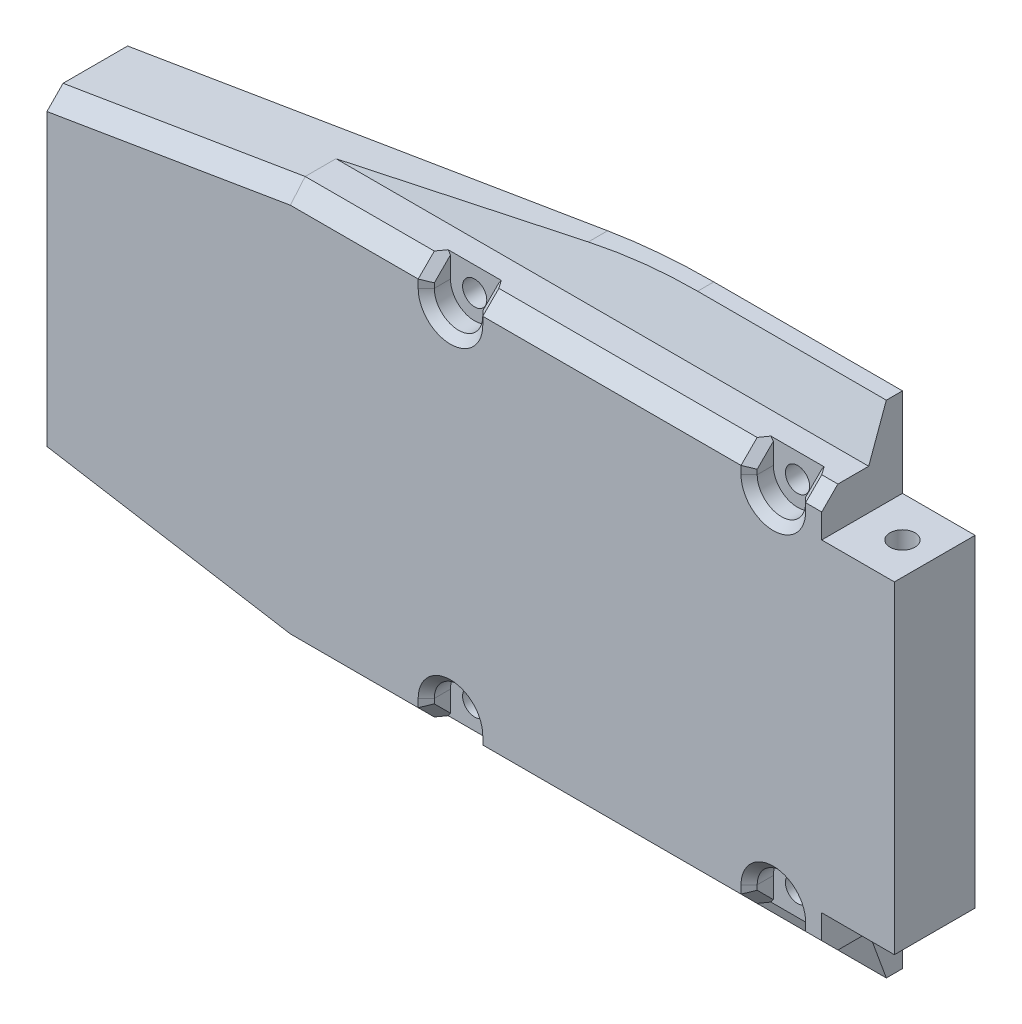
SolidWorks part; units mm, degrees
material "ABS"
ref_plane "Ebene vorne" through (0, 0, 0) normal (0, 0, 1) x (1, 0, 0)
ref_plane "Ebene oben" through (0, 0, 0) normal (0, 1, 0) x (1, 0, 0)
ref_plane "Ebene rechts" through (0, 0, 0) normal (1, 0, 0) x (0, 0, -1)
sketch "Skizze2" plane through (0, 0, 0) normal (0, 0, 1) x (1, 0, 0)
  line L0 (-151.7782, 0) -> (154.8922, 0) construction
  line L1 (0, 106.9611) -> (0, -93.0562) construction
  line L2 (0, 25) -> (-75, 25)
  line L3 (-75, 25) -> (-105, 20)
  line L4 (-105, 20) -> (-105, 11)
  line L5 (-105, 11) -> (-98, 11)
  line L6 (-95, 8) -> (-95, -8)
  line L7 (0, 25) -> (0, -25)
  line L8 (-105, -11) -> (-98, -11)
  line L9 (-105, -20) -> (-105, -11)
  line L10 (-75, -25) -> (-105, -20)
  line L11 (0, -25) -> (-75, -25)
  arc A0 (-98, -11) -> (-95, -8) centre (-98, -8) ccw
  arc A1 (-95, 8) -> (-98, 11) centre (-98, 8) ccw
  point P13 (0, 0)
  point P14 (-95, 0)
  point P19 (-95, -11)
  point P22 (-95, 11)
  dimension "D7" = 3
  dimension "D1" = 105
  dimension "D2" = 50
  dimension "D3" = 40
  dimension "D4" = 30
  dimension "D5" = 22
  dimension "D6" = 10
extrude "Aufsatz-Linear austragen1" add sketch "Skizze2" along normal blind 5 and the other way blind 5
hole_wizard "Ø3.1 (3.1) Durchmesser Bohrung1" positions "Skizze4" profile "Skizze3" hole size "Ø3.1" standard "ANSI Metrisch"
sketch "Skizze4" plane through (-105, 0, 0) normal (-1, 0, 0) x (0, 0, 1)
  line L0 (0, 37.8153) -> (0, -33.0973) construction
  line L3 (-22.117, 0) -> (22.0161, 0) construction
  point P0 (0, 15)
  point P14 (0, -15)
  dimension "D1" = 30
sketch "Skizze3" plane through (-105, 15, 0) normal (0, 1, 0) x (0, 0, 1)
  line L0 (0, 0) -> (0, 8.9313)
  line L1 (0, 8.9313) -> (1.55, 8)
  line L2 (1.55, 8) -> (1.55, 0)
  line L5 (1.55, 0) -> (0, 0)
  line L10 (0, 8.9313) -> (-1.55, 8) construction
  line L11 (0, -6.35) -> (0, 107.95) construction
  dimension "Bohrerdurchmesser" = 3.1
  dimension "Bohrungstiefe" = 8
  dimension "Spitzenwinkel" = 118
sketch "Skizze5" plane through (0, 0, 0) normal (0, 0, 1) x (1, 0, 0)
  line L0 (-134.3407, 0) -> (33.9152, 0) construction
  line L1 (0, 49.9151) -> (0, -37.4044) construction
  circle A0 centre (-55, 22) radius 1.5
  circle A1 centre (-15, 22) radius 1.5
  circle A2 centre (-15, -22) radius 1.5
  circle A3 centre (-55, -22) radius 1.5
  dimension "D1" = 3
  dimension "D2" = 40
  dimension "D3" = 15
  dimension "D4" = 22
extrude "Schnitt-Linear austragen1" cut sketch "Skizze5" against normal through all and the other way through all
sketch "Skizze6" plane through (0, 0, 5) normal (0, 0, 1) x (1, 0, 0)
  line L0 (-55, 22) -> (-55, 29.2626) construction
  line L1 (-58, 22) -> (-58, 29.2626)
  line L2 (-52, 22) -> (-52, 29.2626)
  line L3 (-15, 22) -> (-15, 29.2626) construction
  line L4 (-18, 22) -> (-18, 29.2626)
  line L5 (-12, 22) -> (-12, 29.2626)
  line L6 (-55, -22) -> (-55, -29.7807) construction
  line L7 (-52, -22) -> (-52, -29.7807)
  line L8 (-58, -22) -> (-58, -29.7807)
  line L9 (-15, -22) -> (-15, -30.8486) construction
  line L10 (-12, -22) -> (-12, -30.8486)
  line L11 (-18, -22) -> (-18, -30.8486)
  arc A4 (-58, 22) -> (-52, 22) centre (-55, 22) ccw
  arc A5 (-52, 29.2626) -> (-58, 29.2626) centre (-55, 29.2626) ccw
  arc A6 (-18, 22) -> (-12, 22) centre (-15, 22) ccw
  arc A7 (-12, 29.2626) -> (-18, 29.2626) centre (-15, 29.2626) ccw
  arc A8 (-52, -22) -> (-58, -22) centre (-55, -22) ccw
  arc A9 (-58, -29.7807) -> (-52, -29.7807) centre (-55, -29.7807) ccw
  arc A10 (-12, -22) -> (-18, -22) centre (-15, -22) ccw
  arc A11 (-18, -30.8486) -> (-12, -30.8486) centre (-15, -30.8486) ccw
  point P6 (-15, 25.6313)
  point P12 (-55, 25.6313)
  point P19 (-55, -25.8903)
  point P28 (-15, -26.4243)
  dimension "D1" = 3
extrude "Schnitt-Linear austragen2" cut sketch "Skizze6" against normal blind 3
sketch "Skizze7" plane through (0, 0, 5) normal (0, 0, 1) x (1, 0, 0)
  line L0 (-130.6386, 0) -> (13.2343, 0) construction
  line L1 (0, 46.5959) -> (0, -35.1065) construction
  line L2 (0, 25) -> (-9, 25)
  line L3 (0, 25) -> (-12, 25) construction
  line L4 (-9, 25) -> (-9, 20)
  line L5 (-9, 20) -> (0, 20)
  line L6 (0, 20) -> (0, 25)
  line L7 (0, -20) -> (0, -25)
  line L8 (-9, -20) -> (0, -20)
  line L9 (-9, -25) -> (-9, -20)
  line L10 (0, -25) -> (-9, -25)
  dimension "D1" = 5
  dimension "D2" = 9
extrude "Schnitt-Linear austragen3" cut sketch "Skizze7" against normal through all and the other way through all
sketch "Skizze8" plane through (0, 0, 0) normal (0, 0, 1) x (1, 0, 0)
  line L0 (-143.7875, 0) -> (29.5748, 0) construction
  line L1 (0, 40.8512) -> (0, -33.9576) construction
  line L17 (-55, 30.597) -> (-55, -26.6464) construction
  line L18 (-51, -22) -> (-19, -22)
  line L19 (-56, 18.127) -> (-56, -18.127)
  line L20 (-54, 18.127) -> (-54, -18.127)
  line L21 (-59, -22) -> (-74.7517, -22)
  line L22 (-74.7517, -22) -> (-93, -18.9586)
  line L23 (-93, -18.9586) -> (-93, 18.9586)
  line L24 (-75, -25) -> (-58, -25) construction
  line L25 (-105, -20) -> (-75, -25) construction
  line L26 (-95, 8) -> (-95, -8) construction
  line L27 (-74.7517, 22) -> (-93, 18.9586)
  line L28 (-59, 22) -> (-74.7517, 22)
  line L29 (-51, 22) -> (-19, 22)
  line L30 (-15, -18) -> (-7, -18)
  line L31 (-7, -18) -> (-7, 18)
  line L32 (-15, 18) -> (-7, 18)
  arc A6 (-56, -18.127) -> (-59, -22) centre (-55, -22) ccw
  arc A7 (-54, -18.127) -> (-51, -22) centre (-55, -22) cw
  arc A8 (-54, 18.127) -> (-51, 22) centre (-55, 22) ccw
  arc A9 (-56, 18.127) -> (-59, 22) centre (-55, 22) cw
  arc A10 (-19, -22) -> (-15, -18) centre (-15, -22) cw
  arc A11 (-19, 22) -> (-15, 18) centre (-15, 22) ccw
  point P16 (-56, 0)
  point P29 (-93, 0)
  point P30 (-54, 0)
  point P41 (-7, 0)
  dimension "D3" = 4
  dimension "D1" = 2
  dimension "D2" = 3
  dimension "D4" = 2
  dimension "D5" = 3
  dimension "D6" = 7
extrude "Schnitt-Linear austragen4" cut sketch "Skizze8" against normal through all and the other way blind 4
sketch "Skizze9" plane through (0, 0, -5) normal (0, 0, -1) x (-1, 0, 0)
  line L0 (-28.3161, 0) -> (120.4033, 0) construction
  line L1 (0, 48.4649) -> (0, -32.3525) construction
  line L2 (9, 25) -> (9, 31)
  line L3 (9, 31) -> (39, 31)
  line L7 (9, 25) -> (75, 25)
  line L8 (9, -25) -> (75, -25)
  line L11 (9, -31) -> (39, -31)
  line L12 (9, -25) -> (9, -31)
  line L13 (39, 31) -> (75, 25)
  line L14 (39, -31) -> (75, -25)
  line L15 (75, 25) -> (105, 20) construction
  dimension "D1" = 6
extrude "Aufsatz-Linear austragen2" add sketch "Skizze9" against normal blind 2
hole_wizard "Ø3.1 (3.1) Durchmesser Bohrung2" positions "Skizze11" profile "Skizze10" hole size "Ø3.1" standard "ANSI Metrisch"
sketch "Skizze11" plane through (0, 20, 0) normal (0, 1, 0) x (1, 0, 0)
  line L0 (14.2177, 0) -> (-26.5383, 0) construction
  point P0 (-4, 0)
  dimension "D1" = 4
sketch "Skizze10" plane through (-4, 20, 0) normal (1, 0, 0) x (0, 0, 1)
  line L0 (0, 0) -> (0, 10.9313)
  line L1 (0, 10.9313) -> (1.55, 10)
  line L2 (1.55, 10) -> (1.55, 0)
  line L5 (1.55, 0) -> (0, 0)
  line L10 (0, 10.9313) -> (-1.55, 10) construction
  line L11 (0, -6.35) -> (0, 107.95) construction
  dimension "Bohrerdurchmesser" = 3.1
  dimension "Bohrungstiefe" = 10
  dimension "Spitzenwinkel" = 118
mirror "Spiegeln1" about plane through (0, 0, 0) normal (0, 1, 0) of "Ø3.1 (3.1) Durchmesser Bohrung2"
chamfer "Fase1" distance 6 angle 20 1 edges at (-42, 25, -3) first distance on face at (-33, 28, -3)
chamfer "Fase2" distance 6 angle 20 1 edges at (-42, -25, -3) first distance on face at (-33, -28, -3)
fillet "Verrundung1" radius 80 2 edges at (-39, 31, -4) (-39, -31, -4)
fillet "Verrundung2" radius 2 14 edges at (-7, 18, -0.5) (-19, 22, -0.5) (-51, 22, -0.5) (-54, 18.127, -0.5) (-56, 18.127, -0.5) (-59, 22, -0.5) (-93, 18.9586, -0.5) (-93, -18.9586, -0.5) (-59, -22, -0.5) (-56, -18.127, -0.5) (-54, -18.127, -0.5) (-51, -22, -0.5) (-19, -22, -0.5) (-7, -18, -0.5)
sketch "Skizze12" plane through (0, 0, 5) normal (0, 0, 1) x (1, 0, 0)
  line L0 (-110.4008, 0) -> (7.7355, 0) construction
  line L1 (0, 42.6084) -> (0, -37.939) construction
  line L2 (-105, 11) -> (-105, -11)
  line L3 (-105, -11) -> (-95, -11)
  line L4 (-95, -11) -> (-95, 11)
  line L5 (-95, 11) -> (-105, 11)
  line L6 (-105, 20) -> (-105, 11) construction
  line L7 (-95, 8) -> (-95, -8) construction
extrude "Aufsatz-Linear austragen3" add sketch "Skizze12" against normal blind 1
chamfer "Fase3" distance 2 angle 45 8 edges at (-10.5, -25, 5) (-35, -25, 5) (-66.5, -25, 5) (-90, -22.5, 5) (-10.5, 25, 5) (-35, 25, 5) (-66.5, 25, 5) (-90, 22.5, 5)
fillet "Verrundung3" [suppressed] radius 1.5
sketch "Skizze13" plane through (0, 0, -5) normal (0, 0, -1) x (-1, 0, 0)
  line L0 (4, 10) -> (4, -10) construction
  line L1 (5.5, 10) -> (5.5, -10)
  line L2 (2.5, 10) -> (2.5, -10)
  line L3 (-14.13, 0) -> (38.0816, 0) construction
  arc A0 (5.5, 10) -> (2.5, 10) centre (4, 10) ccw
  arc A1 (2.5, -10) -> (5.5, -10) centre (4, -10) ccw
  point P4 (4, 0)
  dimension "D1" = 3
  dimension "D2" = 4
  dimension "D3" = 20
extrude "Schnitt-Linear austragen5" cut sketch "Skizze13" against normal up to surface (9 mm away) up to face at (-30.8946, 0, 4)
chamfer "Fase4" distance 1 angle 45 20 edges at (-12, -24, 4) (-18, -24, 4) (-12, -22.5, 5) (-18, -22.5, 5) (-15, -19, 5) (-58, 24, 4) (-52, 24, 4) (-58, 22.5, 5) (-52, 22.5, 5) (-55, 19, 5) (-18, 24, 4) (-12, 24, 4) (-18, 22.5, 5) (-12, 22.5, 5) (-15, 19, 5) (-52, -22.5, 5) (-58, -22.5, 5) (-55, -19, 5) (-58, -24, 4) (-52, -24, 4)
ref_axis "Achse1" through (-110.25, 0, 0) along (1, 0, 0)
ref_axis "Achse2" through (0, 0, -5.5) along (0, 0, 1)
ref_axis "Achse3" through (0, 34.1, 0) along (0, -1, 0)
